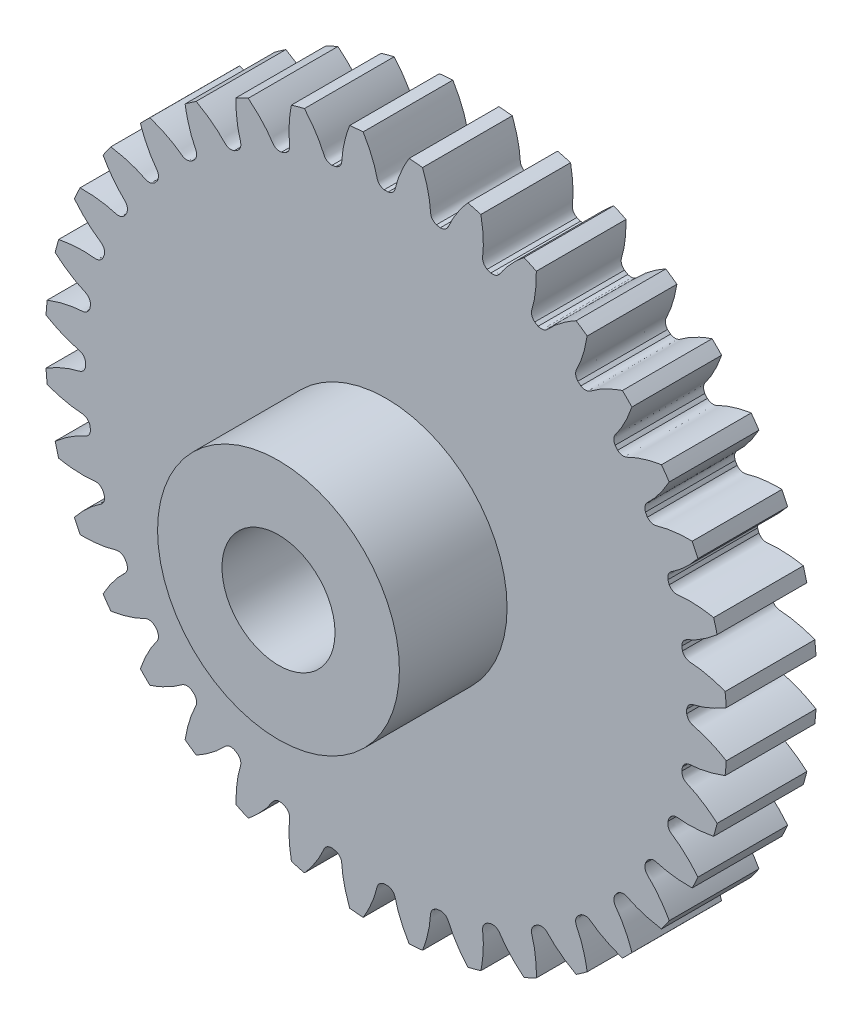
SolidWorks part; units mm, degrees
ref_plane "前视基准面" through (0, 0, 0) normal (0, 0, 1) x (1, 0, 0)
ref_plane "上视基准面" through (0, 0, 0) normal (0, 1, 0) x (1, 0, 0)
ref_plane "右视基准面" through (0, 0, 0) normal (1, 0, 0) x (0, 0, -1)
other "Configuration Table"
sketch "草图1" plane through (0, 0, 0) normal (0, 0, 1) x (1, 0, 0)
  circle A0 centre (0, 0) radius 9.5
extrude "凸台-拉伸1" add sketch "草图1" along normal blind 2.5
ref_axis "基准轴1" through (0, 0, 2.5) along (0, 0, -1)
sketch "草图2" plane through (0, 0, 0) normal (0, 0, 1) x (1, 0, 0)
  line L0 (0, 0) -> (0, 9.5) construction
  circle A0 centre (0, 0) radius 9.5 construction
  arc A1 (0.0549, 8.3748) -> (-0.0549, 8.3748) centre (0, 0) ccw
  arc A2 (1.757, 10.7884) -> (-1.757, 10.7884) centre (0, 0) ccw
  spline S0 degree 3 poles (0.0549, 8.3748) (0.235, 8.4152) (0.2505, 8.5493) (0.2882, 8.6914) (0.2997, 8.7319) (0.3131, 8.7753) (0.3284, 8.8217) (0.3457, 8.871) (0.3652, 8.9231) (0.3869, 8.9779) (0.4111, 9.0354) (0.4378, 9.0956) (0.4671, 9.1582) (0.4992, 9.2232) (0.5341, 9.2907) (0.5719, 9.3603) (0.6128, 9.4322) (0.6569, 9.5061) (0.7043, 9.582) (0.755, 9.6598) (0.8091, 9.7393) (0.8668, 9.8205) (0.9281, 9.9032) (0.9931, 9.9874) (1.0619, 10.0729) (1.1346, 10.1596) (1.2112, 10.2474) (1.2919, 10.3361) (1.3766, 10.4256) (1.4655, 10.5159) (1.5912, 10.6386) (1.6895, 10.7288) (1.757, 10.7884) knots 0 0 0 0 0.120371 0.133303 0.147364 0.162556 0.178878 0.19633 0.214913 0.234626 0.255469 0.277443 0.300547 0.324782 0.350146 0.376641 0.404267 0.433023 0.462909 0.493925 0.526072 0.559349 0.593757 0.629294 0.665963 0.703761 0.74269 0.782749 0.823939 0.866258 0.909709 1 1 1 1
  spline S1 degree 3 poles (-0.0549, 8.3748) (-0.235, 8.4152) (-0.2505, 8.5493) (-0.2882, 8.6914) (-0.2997, 8.7319) (-0.3131, 8.7753) (-0.3284, 8.8217) (-0.3457, 8.871) (-0.3652, 8.9231) (-0.3869, 8.9779) (-0.4111, 9.0354) (-0.4378, 9.0956) (-0.4671, 9.1582) (-0.4992, 9.2232) (-0.5341, 9.2907) (-0.5719, 9.3603) (-0.6128, 9.4322) (-0.6569, 9.5061) (-0.7043, 9.582) (-0.755, 9.6598) (-0.8091, 9.7393) (-0.8668, 9.8205) (-0.9281, 9.9032) (-0.9931, 9.9874) (-1.0619, 10.0729) (-1.1346, 10.1596) (-1.2112, 10.2474) (-1.2919, 10.3361) (-1.3766, 10.4256) (-1.4655, 10.5159) (-1.5912, 10.6386) (-1.6895, 10.7288) (-1.757, 10.7884) knots 0 0 0 0 0.120371 0.133303 0.147364 0.162556 0.178878 0.19633 0.214913 0.234626 0.255469 0.277443 0.300547 0.324782 0.350146 0.376641 0.404267 0.433023 0.462909 0.493925 0.526072 0.559349 0.593757 0.629294 0.665963 0.703761 0.74269 0.782749 0.823939 0.866258 0.909709 1 1 1 1
extrude "切除-拉伸1" cut sketch "草图2" along normal through all
pattern_circular "阵列(圆周)1" count 36 every 10 about axis through (0, 0, 2.5) along (0, 0, -1) of "切除-拉伸1"
sketch "草图3" plane through (0, 0, 0) normal (0, 0, 1) x (1, 0, 0)
  circle A0 centre (0, 0) radius 9 construction
  dimension "Dn" = 18
sketch "草图4" plane through (0, 0, 0) normal (0, 0, -1) x (-1, 0, 0)
  circle A0 centre (0, 0) radius 3.37
  dimension "D1" = 6.74
extrude "凸台-拉伸2" add sketch "草图4" against normal offset from surface (5.5 mm away) 3 up to face at (0, 0, 2.5) offset beyond the face yes
sketch "草图5" plane through (0, 0, 5.5) normal (0, 0, 1) x (1, 0, 0)
  circle A0 centre (0, 0) radius 1.575
  dimension "D1" = 3.15
extrude "切除-拉伸2" cut sketch "草图5" against normal up to next
